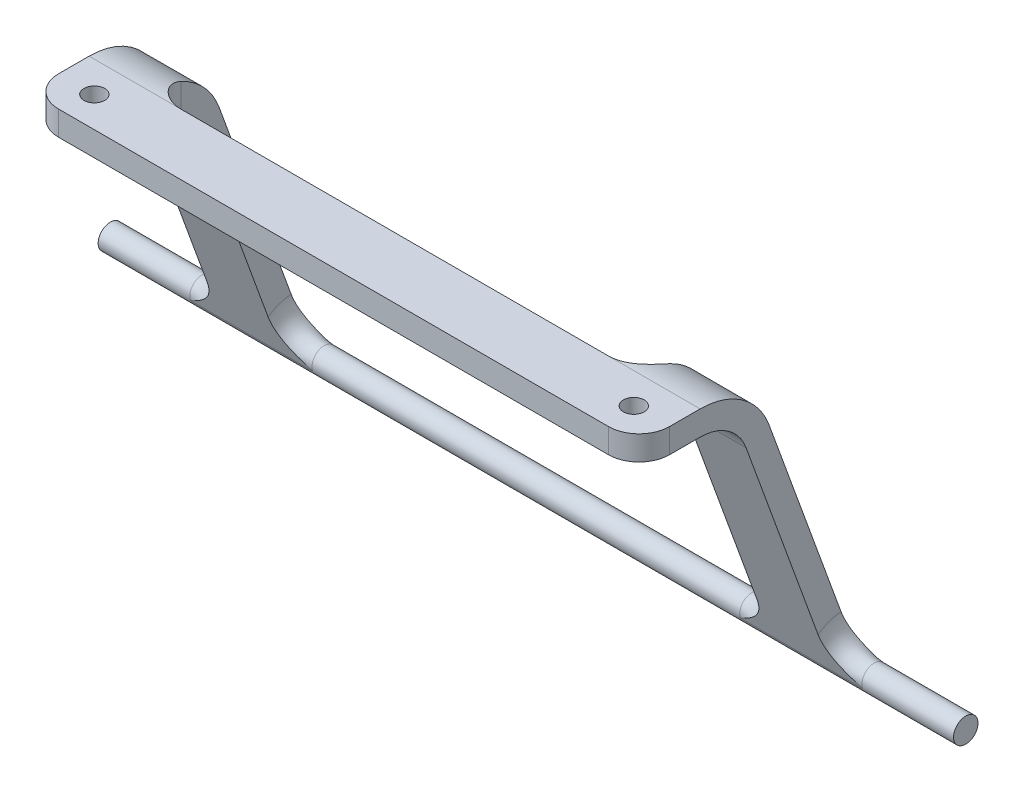
SolidWorks part; units mm, degrees
material "ABS PC"
ref_plane "Front Plane" through (0, 0, 0) normal (0, 0, 1) x (1, 0, 0)
ref_plane "Top Plane" through (0, 0, 0) normal (0, 1, 0) x (1, 0, 0)
ref_plane "Right Plane" through (0, 0, 0) normal (1, 0, 0) x (0, 0, -1)
sketch "Sketch1" plane through (0, 0, 0) normal (0, 1, 0) x (1, 0, 0)
  line L1 (-44.1422, -44.1422) -> (44.1422, -44.1422) construction
  line L2 (-44.1422, -44.1422) -> (-44.1422, 44.1422) construction
  line L3 (-44.1422, 44.1422) -> (44.1422, 44.1422) construction
  line L4 (44.1422, -44.1422) -> (44.1422, 44.1422) construction
  line L5 (-44.1422, -44.1422) -> (44.1422, 44.1422) construction
  line L6 (-44.1422, 44.1422) -> (44.1422, -44.1422) construction
  line L9 (-50, 39.1421) -> (50, 39.1421)
  line L10 (-50, 39.1421) -> (-50, 49.1421)
  line L11 (-50, 49.1421) -> (50, 49.1421)
  line L12 (50, 39.1421) -> (50, 49.1421)
  line L13 (-50, 39.1421) -> (50, 49.1421) construction
  line L14 (-50, 49.1421) -> (50, 39.1421) construction
  circle A0 centre (-44.1422, 44.1422) radius 1.7
  circle A1 centre (44.1422, 44.1422) radius 1.7
  point P0 (0, 0)
  point P8 (0, 44.1422)
  dimension "D2" = 3.4
  dimension "D3" = 3.4
  dimension "D4" = 10
  dimension "D1" = 88.2843
  dimension "D5" = 100
extrude "Boss-Extrude1" add sketch "Sketch1" along normal blind 4
sketch "Sketch3" plane through (50, 0, 0) normal (1, 0, 0) x (0, 0, -1)
  line L0 (49.1421, 4) -> (49.1421, 0) construction
  line L1 (49.1421, -8) -> (49.1421, 0) construction
  line L2 (49.1421, -8) -> (66.0085, -1.8612) construction
  line L3 (56.6597, -5.2638) -> (70.7395, -43.9479)
  line L4 (60.4185, -3.8958) -> (74.4983, -42.5798)
  line L5 (71.2185, -45.2638) -> (74.411, -45.2638) construction
  line L6 (49.1421, 4) -> (49.1421, 0)
  arc A0 (49.1421, 0) -> (56.6597, -5.2638) centre (49.1421, -8) cw
  arc A1 (49.1421, 4) -> (60.4185, -3.8958) centre (49.1421, -8) cw
  arc A2 (70.7395, -43.9479) -> (74.4983, -42.5798) centre (72.6189, -43.2638) ccw
  dimension "D2" = 70
  dimension "D1" = 8
  dimension "D3" = 40
extrude "Boss-Extrude2" add sketch "Sketch3" against normal blind 10
mirror "Mirror8" about plane through (0, 0, 0) normal (1, 0, 0) of "Boss-Extrude2"
sketch "Sketch5" plane through (50, 0, 0) normal (1, 0, 0) x (0, 0, -1)
  line L0 (70.7395, -43.9479) -> (74.4983, -42.5798) construction
  circle A0 centre (72.6189, -43.2638) radius 2
  arc A1 (70.7395, -43.9479) -> (74.4983, -42.5798) centre (72.6189, -43.2638) ccw construction
  arc A2 (70.7395, -43.9479) -> (74.4983, -42.5798) centre (72.6189, -43.2638) ccw construction
  point P7 (72.6189, -43.2638)
extrude "Boss-Extrude3" add sketch "Sketch5" against normal offset from surface 20 and the other way blind 20 up to face at (-50, -10.8255, -55.2054) offset beyond the face yes
fillet "Fillet1" radius 5 4 edges at (-40, -41.3845, -71.9349) (40, -41.3845, -71.9349) (-50, -41.3845, -71.9349) (50, -41.3845, -71.9349)
fillet "Fillet2" radius 5 4 edges at (40, 2, -49.1421) (-40, 2, -49.1421) (-50, 2, -39.1421) (50, 2, -39.1421)
